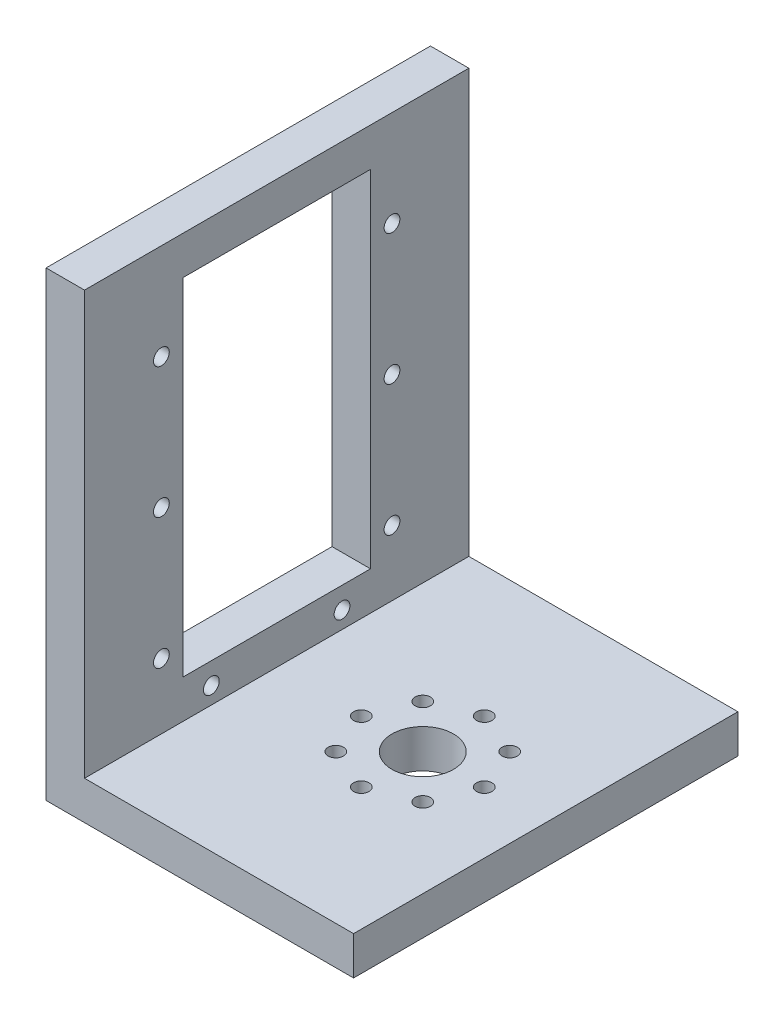
SolidWorks part; units mm, degrees
ref_plane "Front Plane" through (0, 0, 0) normal (0, 0, 1) x (1, 0, 0)
ref_plane "Top Plane" through (0, 0, 0) normal (0, 1, 0) x (1, 0, 0)
ref_plane "Right Plane" through (0, 0, 0) normal (1, 0, 0) x (0, 0, -1)
sketch "Sketch1" plane through (0, 0, 0) normal (0, 1, 0) x (1, 0, 0)
  line L0 (40, 25) -> (24, 25) construction
  line L1 (0, 0) -> (40, 0)
  line L2 (0, 0) -> (0, 50)
  line L3 (0, 50) -> (40, 50)
  line L4 (40, 0) -> (40, 50)
  line L5 (24, 33) -> (24, 25) construction
  circle A0 centre (24, 25) radius 4
  circle A1 centre (24, 33) radius 1
  circle A2 centre (29.6569, 30.6569) radius 1
  circle A3 centre (32, 25) radius 1
  circle A4 centre (29.6569, 19.3431) radius 1
  circle A5 centre (24, 17) radius 1
  circle A6 centre (18.3431, 19.3431) radius 1
  circle A7 centre (16, 25) radius 1
  circle A8 centre (18.3431, 30.6569) radius 1
  point P11 (0, 0)
  point P26 (24, 25)
  dimension "D3" = 8
  dimension "D5" = 2
  dimension "D1" = 40
  dimension "D2" = 50
  dimension "D4" = 16
  dimension "D7" = 8
  dimension "D6" = 8
extrude "Boss-Extrude1" add sketch "Sketch1" along normal blind 5
sketch "Sketch3" plane through (0, 0, 0) normal (0, 1, 0) x (1, 0, 0)
  line L0 (40, 50) -> (0, 50) construction
  line L1 (0, 0) -> (5, 0)
  line L2 (0, 0) -> (0, 50)
  line L3 (0, 50) -> (5, 50)
  line L4 (5, 0) -> (5, 50)
  dimension "D1" = 5
extrude "Boss-Extrude2" add sketch "Sketch3" along normal blind 60
sketch "Sketch4" plane through (0, 0, 0) normal (-1, 0, 0) x (0, 0, 1)
  line L0 (-25, 60) -> (-25, 23.7384) construction
  line L1 (-50, 60) -> (0, 60) construction
  line L2 (-40, 47.5) -> (-10, 47.5) construction
  line L3 (-37.2, 10) -> (-12.8, 10)
  line L4 (-37.2, 10) -> (-37.2, 55)
  line L5 (-37.2, 55) -> (-12.8, 55)
  line L6 (-12.8, 10) -> (-12.8, 55)
  line L7 (-40, 30.5) -> (-10, 30.5) construction
  line L8 (-40, 13.5) -> (-33.5, 7.2) construction
  line L9 (-40, 30.5) -> (-40, 13.5) construction
  circle A0 centre (-40, 47.5) radius 1.025
  circle A1 centre (-10, 47.5) radius 1.025
  circle A2 centre (-40, 30.5) radius 1.025
  circle A5 centre (-10, 30.5) radius 1.025
  circle A8 centre (-40, 13.5) radius 1.025
  circle A9 centre (-33.5, 7.2) radius 1.025
  circle A10 centre (-16.5, 7.2) radius 1.025
  circle A11 centre (-10, 13.5) radius 1.025
  point P8 (-25, 55)
  point P9 (-25, 55)
  point P12 (-25, 47.5)
  dimension "D4" = 2.05
  dimension "D1" = 24.4
  dimension "D2" = 45
  dimension "D3" = 30
  dimension "D5" = 17
  dimension "D6" = 7.5
  dimension "D7" = 17
  dimension "D8" = 6.5
  dimension "D9" = 6.3
  dimension "D10" = 5
extrude "Cut-Extrude1" cut sketch "Sketch4" against normal through all
